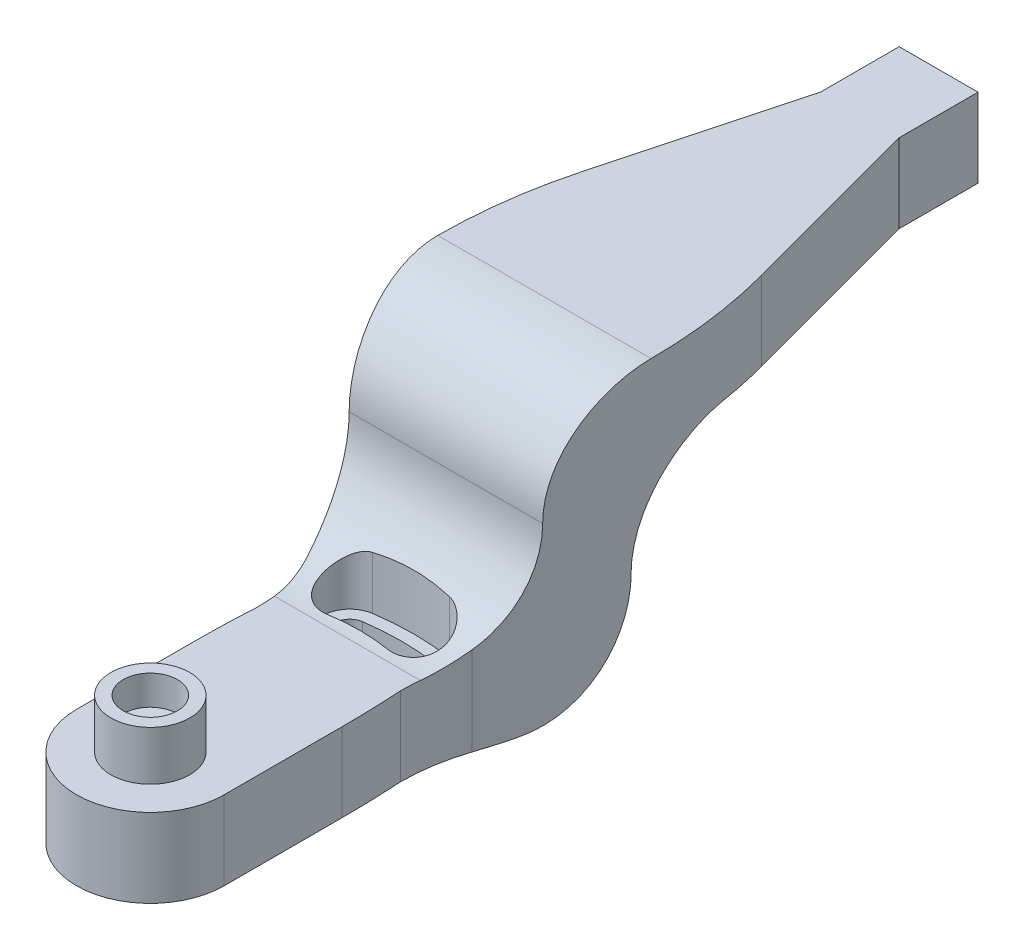
SolidWorks part; units mm, degrees
ref_plane "Front Plane" through (0, 0, 0) normal (0, 0, 1) x (1, 0, 0)
ref_plane "Top Plane" through (0, 0, 0) normal (0, 1, 0) x (1, 0, 0)
ref_plane "Right Plane" through (0, 0, 0) normal (1, 0, 0) x (0, 0, -1)
sketch "Sketch1" plane through (0, 0, 0) normal (0, 1, 0) x (1, 0, 0)
  line L0 (-7.5, 0) -> (-7.5, 11.9327)
  line L1 (7.5, 0) -> (7.5, 11.9327)
  line L3 (-4, 72) -> (4, 72) construction
  line L5 (-4, 72) -> (-4, 80)
  line L6 (-4, 80) -> (4, 80)
  line L7 (4, 80) -> (4, 72)
  line L8 (0, -1.5) -> (0, 25.5) construction
  line L9 (3.5, 23.7434) -> (3.5, 30) construction
  line L10 (-3.5, 23.7434) -> (-3.5, 30) construction
  line L11 (3.5, 15.8994) -> (3.5, 30) construction
  line L12 (-3.5, 15.8994) -> (-3.5, 30) construction
  line L13 (-1007.312, 18.0615) -> (48992.688, 18.0615) construction
  line L14 (0, 15.8994) -> (0, 30) construction
  line L15 (-4, 72) -> (-9.1195, 52.8939)
  line L16 (0, -1000) -> (0, 49000) construction
  line L17 (4, 72) -> (9.1195, 52.8939)
  line L18 (-9.8226, 30) -> (9.8226, 30)
  arc A0 (-7.5, 0) -> (7.5, 0) centre (0, 0) ccw
  arc A1 (7.5, 11.9327) -> (7.312, 18.0615) centre (-92.5, 11.9327) ccw
  arc A2 (-7.5, 11.9327) -> (-7.312, 18.0615) centre (92.5, 11.9327) cw
  circle A3 centre (0, 0) radius 1.5
  circle A4 centre (0, 0) radius 24 construction
  arc A8 (-3.5, 25.2434) -> (-3.2812, 22.2595) centre (-3.5, 23.7434) ccw
  arc A9 (3.2812, 22.2595) -> (3.5, 25.2434) centre (3.5, 23.7434) ccw
  arc A10 (3.2812, 22.2595) -> (-3.2812, 22.2595) centre (0, 0) ccw
  arc A11 (3.7188, 25.2274) -> (-3.7188, 25.2274) centre (0, 0) ccw
  arc A12 (-7.312, 18.0615) -> (-8.3152, 24.3162) centre (-27.312, 18.0615) ccw
  arc A13 (8.3152, 24.3162) -> (7.312, 18.0615) centre (27.312, 18.0615) ccw
  arc A14 (8.3152, 24.3162) -> (9.1195, 52.8939) centre (-39.1768, 39.9529) ccw
  arc A15 (-8.3152, 24.3162) -> (-9.1195, 52.8939) centre (39.1768, 39.9529) cw
  point P12 (7.5, 15)
  point P15 (-7.5, 15)
  dimension "D1" = 15
  dimension "D8" = 100
  dimension "D9" = 3
  dimension "D10" = 48
  dimension "D11" = 22.5
  dimension "D12" = 3.5
  dimension "D13" = 3.5
  dimension "D14" = 3
  dimension "D15" = 25.5
  dimension "D16" = 1.5
  dimension "D17" = 40
  dimension "D18" = 40
  dimension "D21" = 50
  dimension "D2" = 15
  dimension "D3" = 15
  dimension "D4" = 8
  dimension "D5" = 4
  dimension "D6" = 72
  dimension "D7" = 8
  dimension "D19" = 15
  dimension "D20" = 15
  dimension "D22" = 30
extrude "Boss-Extrude1" add sketch "Sketch1" along normal blind 8 contours A2 L0 A0 L1 A1 L7 L6 L5 A11 A9 A10 A8 A3 region at (0, 0, -12.1289)
sketch "Sketch2" plane through (0, 8, 0) normal (0, 1, 0) x (1, 0, 0)
  circle A0 centre (0, 0) radius 4
  circle A1 centre (0, 0) radius 1.5
  dimension "D1" = 8
extrude "Boss-Extrude2" add sketch "Sketch2" along normal blind 2
sketch "Sketch3" plane through (0, 10, 0) normal (0, 1, 0) x (1, 0, 0)
  circle A0 centre (0, 0) radius 4
  circle A1 centre (0, 0) radius 2.75
  dimension "D1" = 5.5
extrude "Boss-Extrude3" add sketch "Sketch3" along normal blind 3
sketch "Sketch4" plane through (0, 8, 0) normal (0, 1, 0) x (1, 0, 0)
  arc A0 (3.099, 21.0228) -> (3.901, 26.464) centre (3.5, 23.7434) ccw
  arc A1 (-3.901, 26.464) -> (-3.099, 21.0228) centre (-3.5, 23.7434) ccw
  arc A2 (3.099, 21.0228) -> (-3.099, 21.0228) centre (0, 0) ccw
  arc A3 (3.901, 26.464) -> (-3.901, 26.464) centre (0, 0) ccw
  dimension "D1" = 5.5
  dimension "D2" = 5.5
extrude "Cut-Extrude1" cut sketch "Sketch4" against normal blind 3
sketch "Sketch5" plane through (0, 0, -30) normal (0, 0, -1) x (-1, 0, 0)
  line L1 (-9.8226, 8) -> (9.8226, 8)
  line L2 (-9.8226, 8) -> (-9.8226, 28)
  line L3 (-9.8226, 28) -> (9.8226, 28)
  line L4 (-9.8226, 0) -> (9.8226, 0)
  line L5 (9.8226, 0) -> (9.8226, 8)
  line L6 (9.8226, 8) -> (-9.8226, 8)
  line L7 (-9.8226, 8) -> (-9.8226, 0)
  line L8 (-9.8226, 0) -> (9.8226, 0)
  line L9 (9.8226, 0) -> (9.8226, 8)
  line L10 (9.8226, 8) -> (-9.8226, 8)
  line L11 (-9.8226, 8) -> (-9.8226, 0)
  line L12 (9.8226, 8) -> (9.8226, 28)
  line L13 (-9.8226, 28) -> (9.8226, 28)
  line L14 (-9.8226, 28) -> (-9.8226, 20)
  line L15 (-9.8226, 20) -> (9.8226, 20)
  line L16 (9.8226, 28) -> (9.8226, 20)
  line M10 (-9.8226, 0) -> (9.8226, 0)
  line M11 (9.8226, 0) -> (9.8226, 8)
  line M12 (9.8226, 8) -> (-9.8226, 8)
  line M13 (-9.8226, 8) -> (-9.8226, 0)
  dimension "D2" = 20
  dimension "D3" = 8
  dimension "D1" = 0
extrude "Boss-Extrude4" add sketch "Sketch5" along normal blind 8 contours L15 L2 L12 M12 | M13 M10 M11 M12 | L2 L15 L12 L3 region at (0, 14, -30) region at (0, 4, -30) region at (0, 24, -30)
extrude "Boss-Extrude5" add sketch "Sketch1<3>" along normal blind 8 from offset 20 contours A15 L18 A14 L17 L7 L6 L5 L15 region at (0, 0, -50.4493)
sketch "Sketch1<3>" plane through (0, 0, 0) normal (0, 1, 0) x (1, 0, 0) same geometry as "Sketch1"
sketch "Sketch6" plane through (0, 20, 0) normal (0, -1, 0) x (1, 0, 0)
  line L0 (-9.8226, -38) -> (-10.785, -38)
  line L8 (9.8226, -38) -> (-9.8226, -38)
  line L9 (-9.8226, -38) -> (-9.8226, -30)
  line L10 (-9.1195, -52.8939) -> (-4, -72)
  line L11 (-4, -72) -> (-4, -80)
  line L12 (-4, -80) -> (4, -80)
  line L13 (4, -80) -> (4, -72)
  line L14 (4, -72) -> (9.1195, -52.8939)
  line L15 (9.8226, -30) -> (9.8226, -38)
  line L16 (10.785, -38) -> (9.8226, -38)
  line L17 (-9.8226, -38) -> (-9.8226, -30)
  line L23 (9.8226, -30) -> (9.8226, -38)
  arc A2 (-9.8226, -30) -> (-9.1195, -52.8939) centre (39.1768, -39.9529) ccw
  arc A3 (9.1195, -52.8939) -> (9.8226, -30) centre (-39.1768, -39.9529) ccw
  arc A4 (-9.8226, -30) -> (-10.785, -38) centre (39.1768, -39.9529) ccw
  arc A5 (10.785, -38) -> (9.8226, -30) centre (-39.1768, -39.9529) ccw
  dimension "D1" = 0
extrude "Boss-Extrude6" add sketch "Sketch6" along normal up to surface (20 mm away) up to face at (0, 0, -19.7633)
fillet "Fillet2" radius 10 4 edges at (0, 0, -38) (0, 8, -30) (0, 28, -30) (0, 20, -38)
